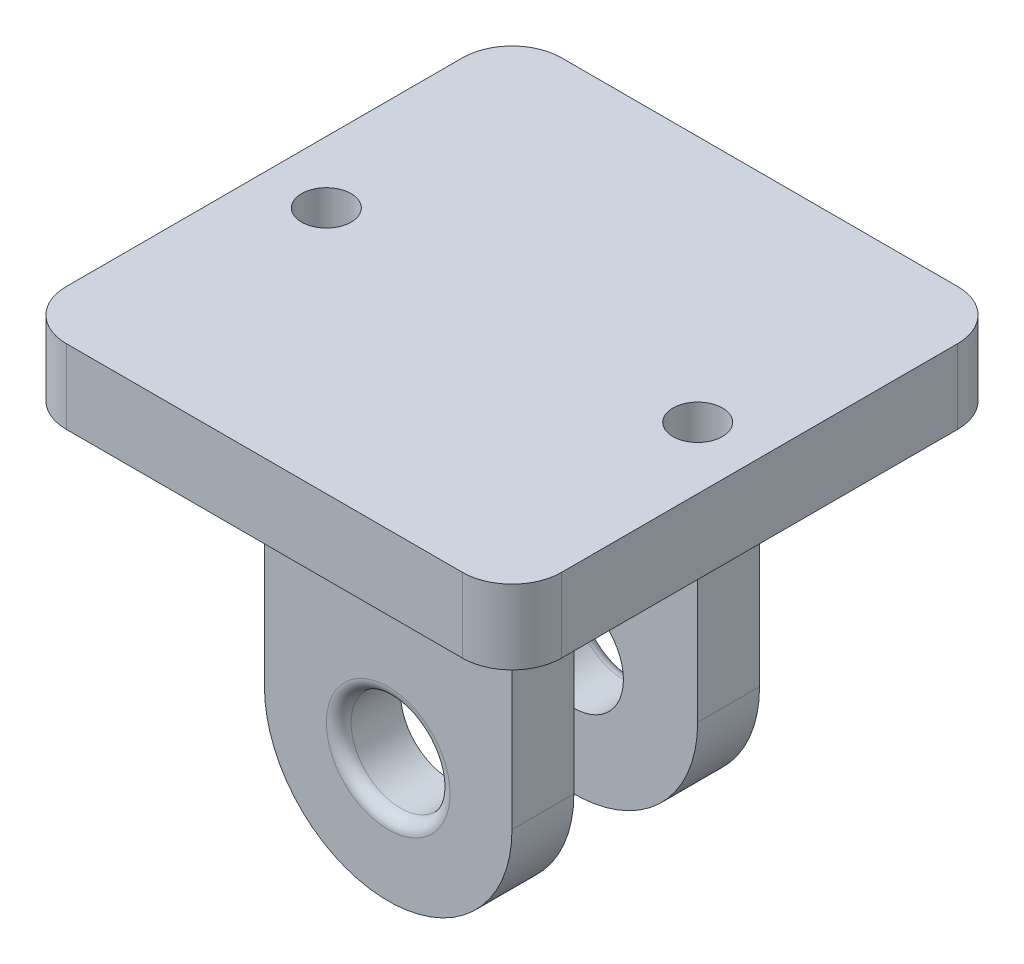
SolidWorks part; units mm, degrees
ref_plane "Plan de face" through (0, 0, 0) normal (0, 0, 1) x (1, 0, 0)
ref_plane "Plan de dessus" through (0, 0, 0) normal (0, 1, 0) x (1, 0, 0)
ref_plane "Plan de droite" through (0, 0, 0) normal (1, 0, 0) x (0, 0, -1)
sketch "Esquisse1" plane through (0, 0, 0) normal (0, 0, 1) x (1, 0, 0)
  line L1 (-5, 7.5) -> (5, 7.5)
  line L2 (-5, 7.5) -> (-5, -7.5)
  line L3 (-5, -7.5) -> (5, -7.5)
  line L4 (5, 7.5) -> (5, -7.5)
  line L5 (-5, 7.5) -> (5, -7.5) construction
  line L6 (-5, -7.5) -> (5, 7.5) construction
  point P0 (0, 0)
  dimension "D1" = 10
  dimension "D2" = 15
extrude "Boss.-Extru.1" add sketch "Esquisse1" along normal blind 10
fillet "Congé1" 2 edges at (-5, -7.5, 5) (5, -7.5, 5) type full round first side face at (-5, 0, 5) second side face at (5, 0, 5) middle face at (0, -7.5, 5)
sketch "Esquisse3" plane through (-5, 0, 0) normal (-1, 0, 0) x (0, 0, 1)
  line L0 (5, 7.5) -> (5, -7.5) construction
  line L1 (10, 7.5) -> (0, 7.5) construction
  line L2 (0, -7.5) -> (10, -7.5) construction
  line L4 (2.5, 4.5) -> (7.5, 4.5)
  line L5 (2.5, 4.5) -> (2.5, -7.5)
  line L6 (2.5, -7.5) -> (7.5, -7.5)
  line L7 (7.5, 4.5) -> (7.5, -7.5)
  line L8 (2.5, 4.5) -> (7.5, -7.5) construction
  line L9 (2.5, -7.5) -> (7.5, 4.5) construction
  point P6 (5, -1.5)
  dimension "D1" = 3
  dimension "D2" = 5
extrude "Enlèv. mat.-Extru.1" cut sketch "Esquisse3" against normal blind 10
sketch "Esquisse4" plane through (0, 7.5, 0) normal (0, 1, 0) x (1, 0, 0)
  line L0 (8, 5) -> (-8, 5)
  line L1 (-10, 3) -> (-10, -13)
  line L2 (-8, -15) -> (8, -15)
  line L3 (10, -13) -> (10, 3)
  line L4 (5, 0) -> (-5, 0)
  line L5 (-5, 0) -> (-5, -10)
  line L6 (-5, -10) -> (5, -10)
  line L7 (5, -10) -> (5, 0)
  line L8 (5, 0) -> (-5, 0)
  line L9 (-5, 0) -> (-5, -10)
  line L10 (-5, -10) -> (5, -10)
  line L11 (5, -10) -> (5, 0)
  line L12 (10, 5) -> (-10, 5) construction
  line L13 (10, -15) -> (10, 5) construction
  line L14 (-10, -15) -> (10, -15) construction
  line L15 (-10, 5) -> (-10, -15) construction
  arc A0 (8, 5) -> (10, 3) centre (8, 3) cw
  arc A1 (8, -15) -> (10, -13) centre (8, -13) ccw
  arc A2 (-10, -13) -> (-8, -15) centre (-8, -13) ccw
  arc A3 (-8, 5) -> (-10, 3) centre (-8, 3) ccw
  line M13 (5, 0) -> (-5, 0)
  line M14 (-5, 0) -> (-5, -10)
  line M15 (-5, -10) -> (5, -10)
  line M16 (5, -10) -> (5, 0)
  dimension "D3" = 2
  dimension "D1" = 0
  dimension "D2" = 5
extrude "Boss.-Extru.2" add sketch "Esquisse4" along normal blind 3 contours M16 M13 M14 M15 | L0 A3 L1 A2 L2 A1 L3 A0 M13 M16 M15 M14 region at (9.2142, 7.5, -4.2142) region at (0, 7.5, 5)
sketch "Esquisse5" plane through (0, 7.5, 0) normal (0, -1, 0) x (1, 0, 0)
  line L0 (-10, 5) -> (-5, 5) construction
  line L1 (-10, -3) -> (-10, 13) construction
  line L2 (10, 13) -> (10, -3) construction
  line L7 (5, 5) -> (10, 5) construction
  circle A0 centre (-7.5, 5) radius 1
  circle A1 centre (7.5, 5) radius 1
  dimension "D1" = 2
  dimension "D2" = 2
extrude "Enlèv. mat.-Extru.2" cut sketch "Esquisse5" against normal blind 3
sketch "Esquisse6" plane through (0, 0, 10) normal (0, 0, 1) x (1, 0, 0)
  circle A0 centre (0, -2.5) radius 2
  arc A1 (-5, -2.5) -> (5, -2.5) centre (0, -2.5) ccw construction
  arc A3 (-5, -2.5) -> (5, -2.5) centre (0, -2.5) ccw
  dimension "4." = 4
extrude "Enlèv. mat.-Extru.3" cut sketch "Esquisse6" against normal through all contours A0 region at (0, -2.5, 10)
fillet "Congé2" radius 0.5 2 edges at (2, -2.5, 10) (2, -2.5, 0)
fillet "Congé3" radius 0.5 4 edges at (-5, 7.5, 5) (0, 7.5, 10) (5, 7.5, 5) (0, 7.5, 0)
